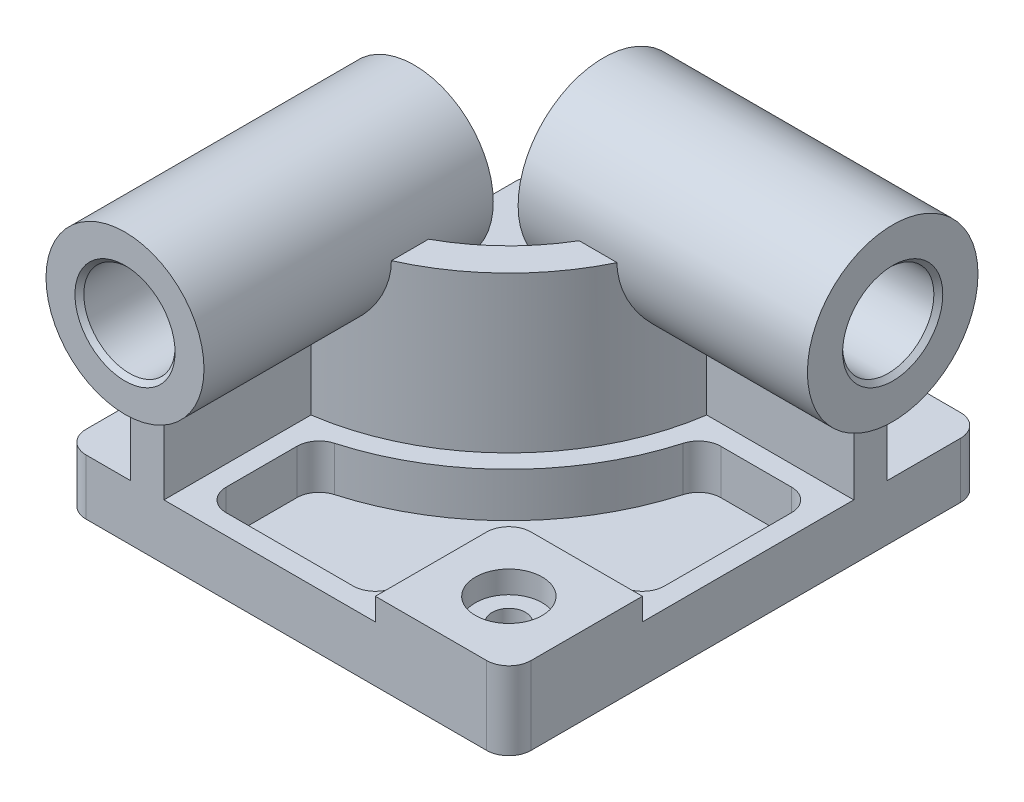
SolidWorks part; units mm, degrees
ref_plane "Front Plane" through (0, 0, 0) normal (0, 0, 1) x (1, 0, 0)
ref_plane "Top Plane" through (0, 0, 0) normal (0, 1, 0) x (1, 0, 0)
ref_plane "Right Plane" through (0, 0, 0) normal (1, 0, 0) x (0, 0, -1)
sketch "Sketch1" plane through (0, 0, 0) normal (0, 1, 0) x (1, 0, 0)
  line L0 (-70, -106.5) -> (-70, -26.5)
  line L1 (-90, 106.5) -> (90, 106.5)
  line L2 (-100, 96.5) -> (-100, -96.5)
  line L3 (-90, -106.5) -> (90, -106.5)
  line L4 (100, 96.5) -> (100, -96.5)
  line L5 (-100, 106.5) -> (100, -106.5) construction
  line L6 (-100, -106.5) -> (100, 106.5) construction
  line L7 (100, 63.5) -> (20, 63.5)
  line L8 (100, 48.5) -> (33.923, 48.5)
  line L9 (-55, -106.5) -> (-55, -40.423)
  line L10 (40, -106.5) -> (40, -56.5)
  line L11 (50, -46.5) -> (100, -46.5)
  arc A0 (-100, -96.5) -> (-90, -106.5) centre (-90, -96.5) ccw
  arc A1 (90, -106.5) -> (100, -96.5) centre (90, -96.5) ccw
  arc A2 (90, 106.5) -> (100, 96.5) centre (90, 96.5) cw
  arc A3 (-90, 106.5) -> (-100, 96.5) centre (-90, 96.5) ccw
  arc A4 (-70, -26.5) -> (20, 63.5) centre (-70, 63.5) ccw
  arc A5 (-55, -40.423) -> (33.923, 48.5) centre (-70, 63.5) ccw
  arc A6 (40, -56.5) -> (50, -46.5) centre (50, -56.5) cw
  point P0 (0, 0)
  dimension "D3" = 10
  dimension "D7" = 90
  dimension "D11" = 10
  dimension "D1" = 213
  dimension "D2" = 200
  dimension "D4" = 80
  dimension "D5" = 170
  dimension "D6" = 170
  dimension "D9" = 60
  dimension "D10" = 60
  dimension "D8" = 15
extrude "Boss-Extrude1" add sketch "Sketch1" along normal blind 95 contours L9 A5 L8 L4 L7 A4 L0 L3 region at (-3.0976, 0, 3.4024)
extrude "Boss-Extrude2" add sketch "Sketch1<3>" along normal blind 25 contours L0 A4 L7 L4 A2 L1 A3 L2 A0 L3 | A5 L9 L3 A1 L4 L8 region at (-31.6903, 0, -39.0093) region at (27.066, 0, 33.566)
sketch "Sketch1<3>" plane through (0, 0, 0) normal (0, 1, 0) x (1, 0, 0) same geometry as "Sketch1"
extrude "Boss-Extrude3" add sketch "Sketch1<4>" along normal blind 35 contours A6 L10 L3 A1 L4 L11 region at (70, 0, 76.5)
sketch "Sketch1<4>" plane through (0, 0, 0) normal (0, 1, 0) x (1, 0, 0) same geometry as "Sketch1"
sketch "Sketch2" plane through (0, 25, 0) normal (0, 1, 0) x (1, 0, 0)
  line L0 (81, 39.5) -> (49.2476, 39.5)
  line L1 (91, -27.5) -> (91, 29.5)
  line L2 (50, -37.5) -> (81, -37.5)
  line L3 (31, -87.5) -> (31, -56.5)
  line L4 (-36, -97.5) -> (21, -97.5)
  line L5 (-46, -55.7476) -> (-46, -87.5)
  line L18 (-55, -106.5) -> (40, -106.5) construction
  line L19 (40, -106.5) -> (40, -56.5) construction
  line L20 (50, -46.5) -> (100, -46.5) construction
  line L21 (100, 48.5) -> (100, -46.5) construction
  line L22 (100, 48.5) -> (33.923, 48.5) construction
  line L23 (-55, -106.5) -> (-55, -40.423) construction
  arc A0 (-38.7419, -46.1309) -> (39.6309, 32.2419) centre (-70, 63.5) ccw
  arc A1 (50, -37.5) -> (31, -56.5) centre (50, -56.5) ccw
  arc A6 (-36, -97.5) -> (-46, -87.5) centre (-36, -87.5) cw
  arc A7 (31, -87.5) -> (21, -97.5) centre (21, -87.5) cw
  arc A8 (91, -27.5) -> (81, -37.5) centre (81, -27.5) cw
  arc A9 (81, 39.5) -> (91, 29.5) centre (81, 29.5) cw
  arc A10 (-55, -40.423) -> (33.923, 48.5) centre (-70, 63.5) ccw construction
  arc A11 (39.6309, 32.2419) -> (49.2476, 39.5) centre (49.2476, 29.5) cw
  arc A12 (-38.7419, -46.1309) -> (-46, -55.7476) centre (-36, -55.7476) ccw
  arc A13 (-55, -40.423) -> (33.923, 48.5) centre (-70, 63.5) ccw construction
  dimension "D3" = 10
  dimension "D1" = 9
  dimension "D2" = 9
  dimension "D8" = 9
  dimension "D9" = 109.6309
  dimension "D4" = 9
  dimension "D5" = 9
  dimension "D6" = 9
  dimension "D7" = 9
extrude "Cut-Extrude1" cut sketch "Sketch2" against normal blind 20
sketch "Sketch4" plane through (100, 0, 0) normal (1, 0, 0) x (0, 0, -1)
  line L0 (96.5, 0) -> (-96.5, 0) construction
  line L1 (63.5, 95) -> (63.5, 25) construction
  circle A0 centre (56, 95) radius 20.5
  circle A1 centre (56, 95) radius 38.3333
  dimension "D2" = 76.6667
  dimension "D3" = 41
  dimension "D1" = 95
  dimension "D4" = 7.5
extrude "Boss-Extrude4" add sketch "Sketch4" against normal blind 120
sketch "Sketch5" plane through (0, 0, 106.5) normal (0, 0, 1) x (1, 0, 0)
  line L0 (-90, 0) -> (90, 0) construction
  line L1 (-55, 95) -> (-55, 25) construction
  circle A0 centre (-62.5, 95) radius 35.5
  circle A1 centre (-62.5, 95) radius 20.5
  dimension "D1" = 71
  dimension "D2" = 41
  dimension "D3" = 95
  dimension "D4" = 7.5
extrude "Boss-Extrude5" add sketch "Sketch5" against normal blind 120
sketch "Sketch6" plane through (0, 0, 106.5) normal (0, 0, 1) x (1, 0, 0)
  line L0 (-70, 95) -> (-55, 95) construction
  circle A0 centre (-62.5, 95) radius 20.5
  circle A1 centre (-62.5, 95) radius 35.5
  dimension "D1" = 71
  dimension "D2" = 41
extrude "Boss-Extrude6" add sketch "Sketch6" along normal blind 10
sketch "Sketch7" plane through (100, 0, 0) normal (1, 0, 0) x (0, 0, -1)
  line L0 (63.5, 95) -> (48.5, 95) construction
  circle A0 centre (56, 95) radius 20.5
  circle A1 centre (56, 95) radius 38.3333
  dimension "D1" = 76.6667
  dimension "D2" = 41
extrude "Boss-Extrude7" add sketch "Sketch7" along normal blind 10
sketch "Sketch8" plane through (0, 0, 116.5) normal (0, 0, 1) x (1, 0, 0)
  circle A0 centre (-62.5, 95) radius 20.5 construction
  circle A3 centre (-62.5, 95) radius 20.5
extrude "Cut-Extrude2" cut sketch "Sketch8" against normal through all contours A3
sketch "Sketch9" plane through (110, 0, 0) normal (1, 0, 0) x (0, 0, -1)
  circle A0 centre (56, 95) radius 20.5 construction
  circle A3 centre (56, 95) radius 20.5
extrude "Cut-Extrude3" cut sketch "Sketch9" against normal through all
sketch "Sketch10" plane through (0, 35, 0) normal (0, 1, 0) x (1, 0, 0)
  line L0 (100, -46.5) -> (100, -96.5) construction
  line L1 (40, -106.5) -> (90, -106.5) construction
  circle A0 centre (70, -76.5) radius 15
  dimension "D3" = 30
  dimension "D1" = 30
  dimension "D2" = 30
extrude "Cut-Extrude4" cut sketch "Sketch10" against normal blind 10
sketch "Sketch11" plane through (0, 25, 0) normal (0, 1, 0) x (1, 0, 0)
  circle A0 centre (70, -76.5) radius 7.5
  dimension "D1" = 15
extrude "Cut-Extrude5" cut sketch "Sketch11" along normal through all and the other way through all
chamfer "Chamfer1" distance 2 angle 45 4 edges at (110, 95, -76.5) (-20, 95, -76.5) (-42, 95, -13.5) (-42, 95, 116.5)
